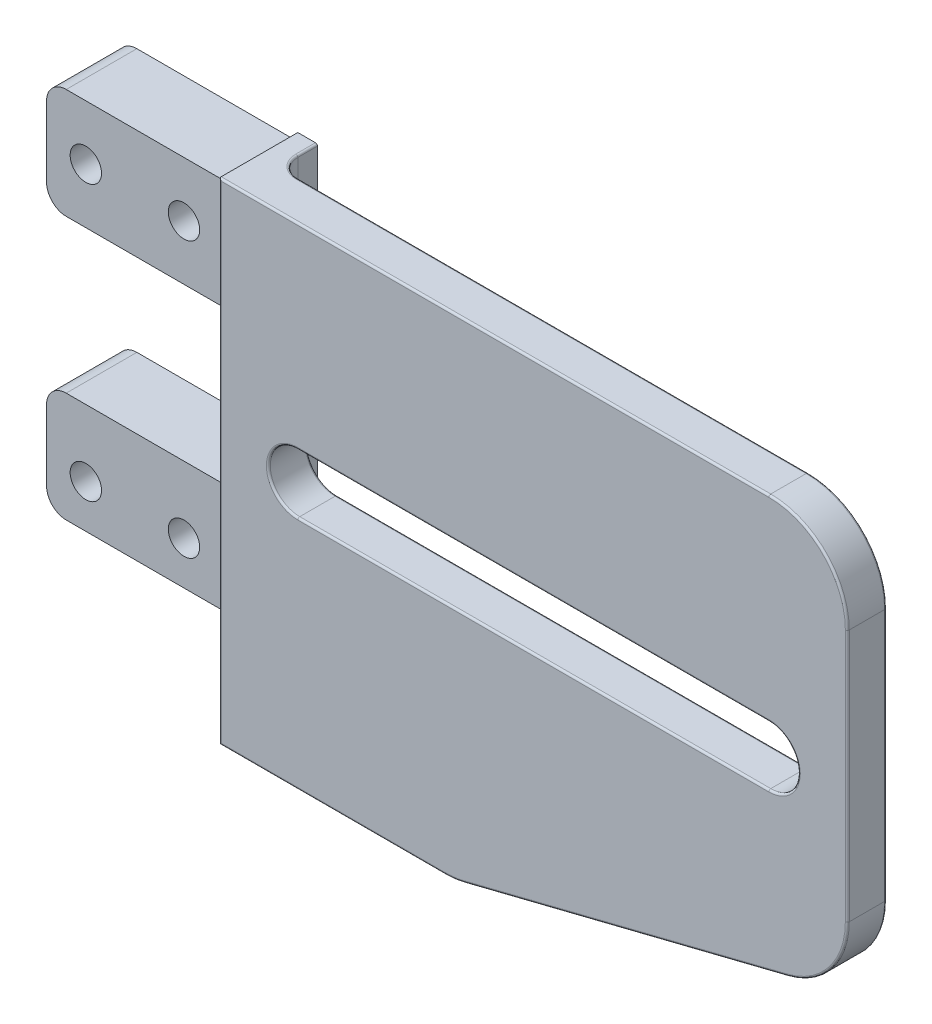
SolidWorks part; units mm, degrees
ref_plane "Ön Düzlem" through (0, 0, 0) normal (0, 0, 1) x (1, 0, 0)
ref_plane "Üst Düzlem" through (0, 0, 0) normal (0, 1, 0) x (1, 0, 0)
ref_plane "Sağ Düzlem" through (0, 0, 0) normal (1, 0, 0) x (0, 0, -1)
sketch "Sketch1" plane through (0, 0, 0) normal (0, 0, 1) x (1, 0, 0)
  line L0 (-80, 62.5) -> (-80, -62.5)
  line L1 (-80, -62.5) -> (-20, -62.5)
  line L2 (-20, -62.5) -> (80, -37.5)
  line L3 (80, -37.5) -> (80, 62.5)
  line L4 (80, 62.5) -> (-80, 62.5)
  line L5 (-80, 0) -> (80, 0) construction
  line L6 (60, 5) -> (-60, 5) construction
  line L7 (60, -2.5) -> (-60, -2.5)
  line L8 (60, 12.5) -> (-60, 12.5)
  line L9 (-80, 61.5) -> (-125, 61.5)
  line L10 (-125, 61.5) -> (-125, 33.5)
  line L11 (-125, 33.5) -> (-80, 33.5)
  line L12 (-80, -5.5) -> (-125, -5.5)
  line L13 (-125, -5.5) -> (-125, -33.5)
  line L14 (-125, -33.5) -> (-80, -33.5)
  line L15 (-125, 47.5) -> (-80, 47.5) construction
  arc A0 (60, -2.5) -> (60, 12.5) centre (60, 5) ccw
  arc A1 (-60, 12.5) -> (-60, -2.5) centre (-60, 5) ccw
  circle A2 centre (-115, 47.5) radius 4
  circle A3 centre (-90, 47.5) radius 4
  circle A4 centre (-115, -22.5) radius 4
  circle A5 centre (-90, -22.5) radius 4
  point P11 (0, 5)
  dimension "D11" = 8
  dimension "D1" = 160
  dimension "D2" = 100
  dimension "D3" = 125
  dimension "D4" = 60
  dimension "D5" = 120
  dimension "D6" = 15
  dimension "D7" = 60
  dimension "D8" = 1
  dimension "D9" = 45
  dimension "D10" = 15
  dimension "D12" = 10
  dimension "D13" = 25
  dimension "D14" = 29
  dimension "D15" = 40
extrude "Boss-Extrude1" add sketch "Sketch1" along normal mid plane 10 contours L3 L4 L0 L1 L2 A1 L8 A0 L7 region at (0, 60.4696, 0)
extrude "Boss-Extrude3" add sketch "Sketch1<3>" along normal offset from surface 1 and the other way blind 14 contours L10 L11 L0 L9 A3 A2 | L13 L14 L0 L12 A5 A4 region at (-102.5, 47.5, 0) region at (-102.5, -19.2399, 0) up to face at (0, 5, 5)
sketch "Sketch1<3>" plane through (0, 0, 0) normal (0, 0, 1) x (1, 0, 0) same geometry as "Sketch1"
fillet "Fillet1" radius 20 3 edges at (-20, -62.5, 0) (80, -37.5, 0) (80, 62.5, 0)
sketch "Sketch2" plane through (0, 0, -5) normal (0, 0, -1) x (-1, 0, 0)
  line L0 (-60, 62.5) -> (80, 62.5) construction
  line L1 (75, 62.5) -> (80, 62.5)
  line L2 (75, 62.5) -> (75, -62.5)
  line L3 (75, -62.5) -> (80, -62.5)
  line L4 (80, 62.5) -> (80, -62.5)
  line L5 (75, 62.5) -> (80, -62.5) construction
  line L6 (75, -62.5) -> (80, 62.5) construction
  line L7 (80, -33.5) -> (80, -62.5) construction
  point P0 (77.5, 0)
  dimension "D1" = 5
extrude "Boss-Extrude4" add sketch "Sketch2" along normal blind 10
fillet "Fillet2" radius 5 5 edges at (-75, 0, -5) (-125, -33.5, -5) (-125, -5.5, -5) (-125, 33.5, -5) (-125, 61.5, -5)
fillet "Fillet4" radius 0.5 27 edges at (-75, -62.5, -12.5) (-73.5355, -62.5, -6.4645) (-75, 62.5, -12.5) (-73.5355, 62.5, -6.4645) (-80, 0, 5) (-10, 62.5, 5) (74.1421, 56.6421, 5) (80, 10.3078, 5) (75.7641, -34.1927, 5) (23.6197, -51.5951, 5) (-20.0184, -62.3502, 5) (-51.2311, -62.5, 5) (0, -2.5, 5) (67.5, 5, 5) (0, 12.5, 5) (-67.5, 5, 5) (-20.0184, -62.3502, -5) (23.6197, -51.5951, -5) (75.7641, -34.1927, -5) (80, 10.3078, -5) (74.1421, 56.6421, -5) (-5, 62.5, -5) (-46.2311, -62.5, -5) (0, 12.5, -5) (67.5, 5, -5) (0, -2.5, -5) (-67.5, 5, -5)
